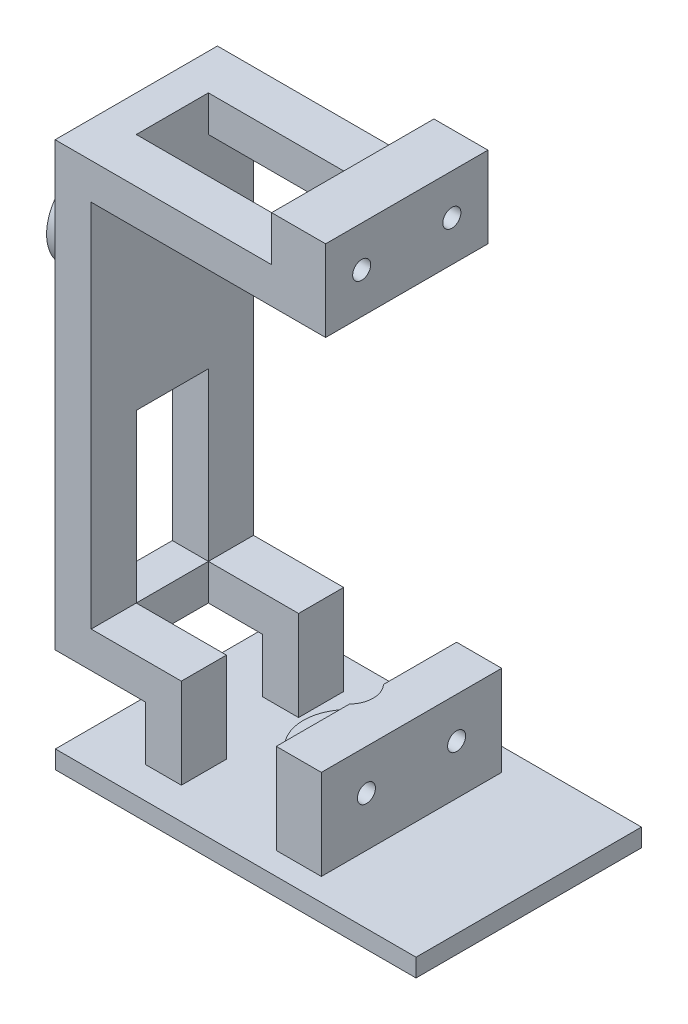
SolidWorks part; units mm, degrees
ref_plane "Front Plane" through (0, 0, 0) normal (0, 0, 1) x (1, 0, 0)
ref_plane "Top Plane" through (0, 0, 0) normal (0, 1, 0) x (1, 0, 0)
ref_plane "Right Plane" through (0, 0, 0) normal (1, 0, 0) x (0, 0, -1)
sketch "Sketch1" plane through (0, 0, 0) normal (0, 1, 0) x (1, 0, 0)
  line L0 (-20, 0) -> (20, 0) construction
  line L1 (-20, -12.5) -> (20, -12.5)
  line L2 (-20, -12.5) -> (-20, 12.5)
  line L3 (-20, 12.5) -> (20, 12.5)
  line L4 (20, -12.5) -> (20, 12.5)
  line L5 (-20, -12.5) -> (20, 12.5) construction
  line L6 (-20, 12.5) -> (20, -12.5) construction
  line L7 (0, 12.5) -> (0, -12.5) construction
  line L8 (-7.9106, 3.9553) -> (7.0894, 3.9553)
  line L9 (-7.9106, 3.9553) -> (-7.9106, -3.5447)
  line L10 (-7.9106, -3.5447) -> (7.0894, -3.5447)
  line L11 (7.0894, 3.9553) -> (7.0894, -3.5447)
  line L12 (-7.9106, 3.9553) -> (7.0894, -3.5447) construction
  line L13 (-7.9106, -3.5447) -> (7.0894, 3.9553) construction
  circle A0 centre (0, 7.9553) radius 1
  circle A1 centre (0, -7.5447) radius 1
  circle A2 centre (16, 0) radius 1
  circle A3 centre (-16, 0) radius 1
  point P0 (0, 0)
  point P8 (0, 0)
  dimension "D5" = 2
  dimension "D7" = 2
  dimension "D9" = 2
  dimension "D1" = 40
  dimension "D2" = 25
  dimension "D3" = 15
  dimension "D4" = 7.5
  dimension "D6" = 4
  dimension "D8" = 4
  dimension "D10" = 16
extrude "Boss-Extrude1" add sketch "Sketch1" along normal blind 2 contours L2 L1 L4 L3
sketch "Sketch2" plane through (0, 2, 0) normal (0, 1, 0) x (1, 0, 0)
  line L1 (2, 10) -> (7, 10)
  line L2 (2, 10) -> (2, -10)
  line L3 (2, -10) -> (7, -10)
  line L4 (7, 10) -> (7, -10)
  line L5 (20, -12.5) -> (20, 12.5) construction
  point P6 (20, 0)
  point P7 (7, 0)
  dimension "D1" = 20
  dimension "D2" = 13
  dimension "D3" = 5
extrude "Boss-Extrude2" add sketch "Sketch2" along normal blind 10
sketch "Sketch4" plane through (7, 0, 0) normal (1, 0, 0) x (0, 0, -1)
  line L0 (-7.046, 10.16) -> (2.954, 10.16) construction
  line L3 (-10, 12) -> (9.965, 12)
  line L4 (-10, 12) -> (-10, 6)
  line L5 (-10, 6) -> (9.965, 6)
  line L6 (9.965, 12) -> (9.965, 6)
  dimension "D1" = 10
  dimension "D2" = 6
extrude "Boss-Extrude3" add sketch "Sketch4" against normal up to surface (5 mm away) up to face at (2, 7, 0)
sketch "Sketch5" plane through (7, 0, 0) normal (1, 0, 0) x (0, 0, -1)
  line L0 (-5, 7.5) -> (5, 7.5) construction
  line L1 (-10, 12) -> (10, 12) construction
  circle A0 centre (5, 7.5) radius 1
  circle A1 centre (-5, 7.5) radius 1
  point P4 (0, 12)
  point P5 (0, 7.5)
  dimension "D2" = 2
  dimension "D3" = 2
  dimension "D1" = 10
  dimension "D4" = 4.5
extrude "Cut-Extrude2" cut sketch "Sketch5" against normal up to surface (5 mm away) up to face at (2, 7, 0)
sketch "Sketch6" plane through (0, 2, 0) normal (0, 1, 0) x (1, 0, 0)
  line L0 (-20, 12.5) -> (-20, -12.5) construction
  line L1 (-13.5277, 9) -> (-9.5277, 9)
  line L2 (-13.5277, 9) -> (-13.5277, -9)
  line L3 (-13.5277, -9) -> (-9.5277, -9)
  line L4 (-9.5277, 9) -> (-9.5277, -9)
  line L10 (-13.5277, 4) -> (-9.5277, 4)
  line L11 (-13.5277, 4) -> (-13.5277, -4)
  line L12 (-13.5277, -4) -> (-9.5277, -4)
  line L13 (-9.5277, 4) -> (-9.5277, -4)
  point P6 (-20, 0)
  point P7 (-13.5277, 0)
  point P12 (-13.5277, 0)
  dimension "D1" = 4
  dimension "D2" = 18
  dimension "D3" = 4
  dimension "D4" = 8
extrude "Boss-Extrude4" add sketch "Sketch6" along normal blind 10 contours L12 L2 L3 L4 | L2 L10 L4 L1 region at (-11.5277, 2, -6.5) region at (-11.5277, 2, 6.5)
sketch "Sketch8" plane through (-13.5277, 0, 0) normal (-1, 0, 0) x (0, 0, 1)
  line L1 (-9, 12) -> (-4, 12)
  line L2 (-9, 12) -> (-9, 8)
  line L3 (-9, 8) -> (-4, 8)
  line L4 (-4, 12) -> (-4, 8)
  dimension "D1" = 5
  dimension "D2" = 4
ref_plane "Plane1" through (0, 0, 0) normal (0, 0, -1) x (-1, 0, 0)
extrude "Boss-Extrude5" add sketch "Sketch8" along normal blind 10
mirror "Mirror1" about plane through (0, 0, 0) normal (0, 0, -1) of "Boss-Extrude5"
sketch "Sketch9" plane through (0, 12, 0) normal (0, 1, 0) x (1, 0, 0)
  line L0 (-23.5277, 4) -> (-9.5277, 4) construction
  line L1 (-23.5277, 9) -> (-19.5277, 9)
  line L2 (-23.5277, 9) -> (-23.5277, 4)
  line L3 (-23.5277, 4) -> (-19.5277, 4)
  line L4 (-19.5277, 9) -> (-19.5277, 4)
  dimension "D1" = 4
  dimension "D2" = 0
extrude "Boss-Extrude6" add sketch "Sketch9" along normal blind 45
mirror "Mirror2" about plane through (0, 0, 0) normal (0, 0, -1) of "Boss-Extrude5"
mirror "Mirror3" about plane through (0, 0, 0) normal (0, 0, -1) of "Boss-Extrude6"
sketch "Sketch12" plane through (-23.5277, 0, 0) normal (-1, 0, 0) x (0, 0, 1)
  line L0 (9, 57) -> (9, 8) construction
  line L1 (-9, 57) -> (9, 57)
  line L2 (-9, 57) -> (-9, 53)
  line L3 (-9, 53) -> (9, 53)
  line L4 (9, 57) -> (9, 53)
  line L5 (-10, 12) -> (10, 12) construction
  line L6 (-9, 8) -> (9, 8)
  line L7 (-9, 8) -> (-9, 12)
  line L8 (-9, 12) -> (9, 12)
  line L9 (9, 8) -> (9, 12)
  line L10 (-9, 32.5) -> (9, 32.5) construction
  line L11 (-9, 57) -> (-9, 8) construction
  line L13 (-9, 30.5) -> (9, 30.5)
  line L14 (-9, 30.5) -> (-9, 34.5)
  line L15 (-9, 34.5) -> (9, 34.5)
  line L16 (9, 30.5) -> (9, 34.5)
  line L17 (-9, 30.5) -> (9, 34.5) construction
  line L18 (-9, 34.5) -> (9, 30.5) construction
  point P18 (0, 32.5)
  dimension "D1" = 4
  dimension "D2" = 4
  dimension "D3" = 4
extrude "Boss-Extrude8" add sketch "Sketch12" against normal up to surface (4 mm away) up to face at (-19.5277, 34.5, 6.5)
sketch "Sketch13" plane through (-19.5277, 0, 0) normal (1, 0, 0) x (0, 0, -1)
  line L1 (-9, 57) -> (-4, 57)
  line L2 (-9, 57) -> (-9, 53)
  line L3 (-9, 53) -> (-4, 53)
  line L4 (-4, 57) -> (-4, 53)
  line L5 (9, 57) -> (4, 57)
  line L6 (9, 57) -> (9, 53)
  line L7 (9, 53) -> (4, 53)
  line L8 (4, 57) -> (4, 53)
extrude "Boss-Extrude9" add sketch "Sketch13" along normal blind 26
sketch "Sketch14" plane through (6.4723, 0, 0) normal (1, 0, 0) x (0, 0, -1)
  line L0 (-9, 57) -> (9, 57)
  line L1 (-9, 57) -> (-9, 53)
  line L2 (9, 57) -> (9, 53)
  line L3 (-9, 53) -> (9, 53)
  line L4 (-9, 53) -> (-4, 53) construction
extrude "Boss-Extrude10" add sketch "Sketch14" against normal blind 6
sketch "Sketch15" plane through (6.4723, 0, 0) normal (1, 0, 0) x (0, 0, -1)
  line L0 (-5, 57.5) -> (5, 57.5) construction
  line L1 (-9, 53) -> (9, 53) construction
  line L2 (-5, 7.5) -> (-5, 57.5) construction
  circle A0 centre (-5, 57.5) radius 1
  circle A1 centre (5, 57.5) radius 1
  dimension "D3" = 2
  dimension "D4" = 2
  dimension "D1" = 10
  dimension "D2" = 4.5
sketch "Sketch16" plane through (0, 57, 0) normal (0, 1, 0) x (1, 0, 0)
  line L0 (6.4723, 9) -> (6.4723, -9)
  line L1 (6.4723, 9) -> (0.4841, 9)
  line L2 (6.4723, -9) -> (0.4841, -9)
  line L3 (0.4841, 9) -> (0.4841, -9)
extrude "Boss-Extrude11" add sketch "Sketch16" along normal blind 5
extrude "Cut-Extrude3" cut sketch "Sketch15" against normal blind 6
sketch "Sketch17" plane through (0, 0, 0) normal (0, -1, 0) x (1, 0, 0)
  circle A0 centre (0, 0) radius 3
  circle A1 centre (0, 0) radius 5
  dimension "D1" = 6
  dimension "D2" = 2
sketch "Sketch18" plane through (-23.5277, 0, 0) normal (-1, 0, 0) x (0, 0, 1)
  line L0 (0, 0) -> (0, 62) construction
  line L1 (-9, 62) -> (9, 62) construction
  line L2 (-17.0412, 42) -> (24.329, 42) construction
  line L3 (12.5, 0) -> (-12.5, 0) construction
  dimension "42" = 42
extrude "Cut-Extrude5" cut sketch "Sketch17" against normal blind 6 contours A0
ref_plane "Plane2" through (0, 1, 0) normal (0, -1, 0) x (-1, 0, 0)
ref_plane "Plane3" through (0, 3, 0) normal (0, 1, 0) x (1, 0, 0)
sketch "Sketch20" plane through (0, 3, 0) normal (0, 1, 0) x (1, 0, 0)
  circle A0 centre (0, 0) radius 3
  circle A1 centre (0, 0) radius 5
  dimension "D1" = 6
  dimension "D2" = 2
sketch "Sketch23" plane through (20, 0, 0) normal (1, 0, 0) x (0, 0, -1)
  line L0 (-12.5, 2) -> (-10.5, 2)
  line L1 (-12.5, 2) -> (-12.5, 59.5)
  line L2 (12.5, 2) -> (12.5, 59.5)
  line L3 (-10.5, 2) -> (-10.5, 59.5)
  line L4 (-12.5, 2) -> (12.5, 2) construction
  line L5 (10.5, 2) -> (10.5, 59.5)
  line L6 (10.5, 2) -> (12.5, 2)
  arc A0 (12.5, 59.5) -> (-12.5, 59.5) centre (0, 59.5) ccw
  arc A1 (10.5, 59.5) -> (-10.5, 59.5) centre (0, 59.5) ccw
  dimension "D2" = 2
sketch "Sketch24" plane through (-23.5277, 0, 0) normal (-1, 0, 0) x (0, 0, 1)
  line L2 (4, 34.5) -> (4, 53) construction
  line L3 (-4, 34.5) -> (4, 34.5)
  line L4 (-4, 34.5) -> (-4, 53)
  line L5 (-4, 53) -> (4, 53)
  line L6 (4, 34.5) -> (4, 53)
  line L7 (-4, 34.5) -> (4, 53) construction
  line L8 (-4, 53) -> (4, 34.5) construction
  line L9 (4, 34.5) -> (-4, 34.5) construction
  line M1 (4, 53) -> (4, 34.5)
  line M3 (-4, 34.5) -> (-4, 53)
extrude "Boss-Extrude18" add sketch "Sketch24" against normal blind 4 contours L5 L3 M3 | L3 L5 M1 region at (-23.5277, 43.75, 0)
extrude "Boss-Extrude20" add sketch "Sketch20" against normal blind 1
sketch "Sketch26" plane through (0, 3, 0) normal (0, 1, 0) x (1, 0, 0)
  circle A0 centre (0, 0) radius 2.9983
  circle A1 centre (0, 0) radius 5
  circle A2 centre (0, 0) radius 1.5
  line M1 (2, -4.5826) -> (2, -2.2361)
  arc M2 (2, -2.2361) -> (2, 2.2361) centre (0, 0) cw
  line M3 (2, 2.2361) -> (2, 4.5826)
  arc M4 (2, 4.5826) -> (2, -4.5826) centre (0, 0) ccw
  dimension "D1" = 3
extrude "Boss-Extrude21" add sketch "Sketch26" along normal blind 1 contours A0 A2 | M4 M1 M2 M3 region at (-2.9135, 3, 0) region at (1.8779, 3, -3.4093)
sketch "Sketch27" plane through (0, 4, 0) normal (0, 1, 0) x (1, 0, 0)
  circle A0 centre (0, 0) radius 5
  circle A1 centre (0, 0) radius 2.75
  dimension "D1" = 5.5
extrude "Boss-Extrude22" add sketch "Sketch27" along normal blind 2
sketch "Sketch28" plane through (0, 6, 0) normal (0, 1, 0) x (1, 0, 0)
  circle A0 centre (0, 0) radius 2.75
extrude "Cut-Extrude10" cut sketch "Sketch28" along normal blind 10
sketch "Sketch29" plane through (-23.5277, 0, 0) normal (-1, 0, 0) x (0, 0, 1)
  circle A0 centre (-0.05, 43.4) radius 5
  point P2 (0, 0)
  point P6 (0, 0)
  dimension "D1" = 10
extrude "Boss-Extrude23" add sketch "Sketch29" along normal blind 5
sketch "Sketch30" plane through (-23.5277, 0, 0) normal (-1, 0, 0) x (0, 0, 1)
  line L0 (-9, 32.5) -> (9, 32.5) construction
  line L1 (-9, 57) -> (-9, 8) construction
  line L2 (9, 57) -> (9, 8) construction
  line L3 (0, 57) -> (0, 8) construction
  line L4 (-9, 57) -> (9, 57) construction
  line L5 (-9, 8) -> (9, 8) construction
equation "\"inner-diameter\"= 10mm"
equation "\"outer-diameter\"= 20mm"
